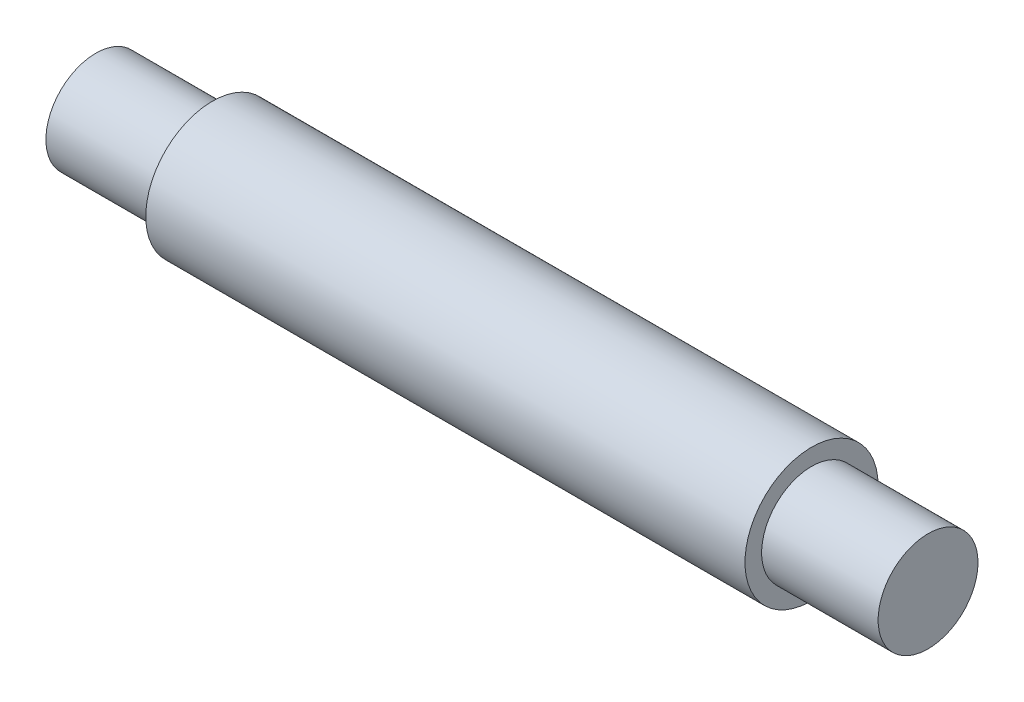
SolidWorks part; units mm, degrees
material "Chrome Stainless Steel"
ref_plane "Front Plane" through (0, 0, 0) normal (1, 0, 0) x (0, 1, 0)
ref_plane "Top Plane" through (0, 0, 0) normal (0, 0, 1) x (0, 1, 0)
ref_plane "Right Plane" through (0, 0, 0) normal (0, 1, 0) x (-1, 0, 0)
sketch "Sketch1" plane through (0, 0, 0) normal (1, 0, 0) x (0, 1, 0)
  circle A0 centre (0, 0) radius 4
  dimension "D1" = 8
extrude "Boss-Extrude1" add sketch "Sketch1" along normal blind 18
sketch "Sketch2" plane through (18, 0, 0) normal (1, 0, 0) x (0, 1, 0)
  circle A0 centre (0, 0) radius 3
  dimension "D1" = 6
extrude "Boss-Extrude2" add sketch "Sketch2" along normal blind 7
mirror "Mirror1" about plane through (0, 0, 0) normal (1, 0, 0) of bodies 102
